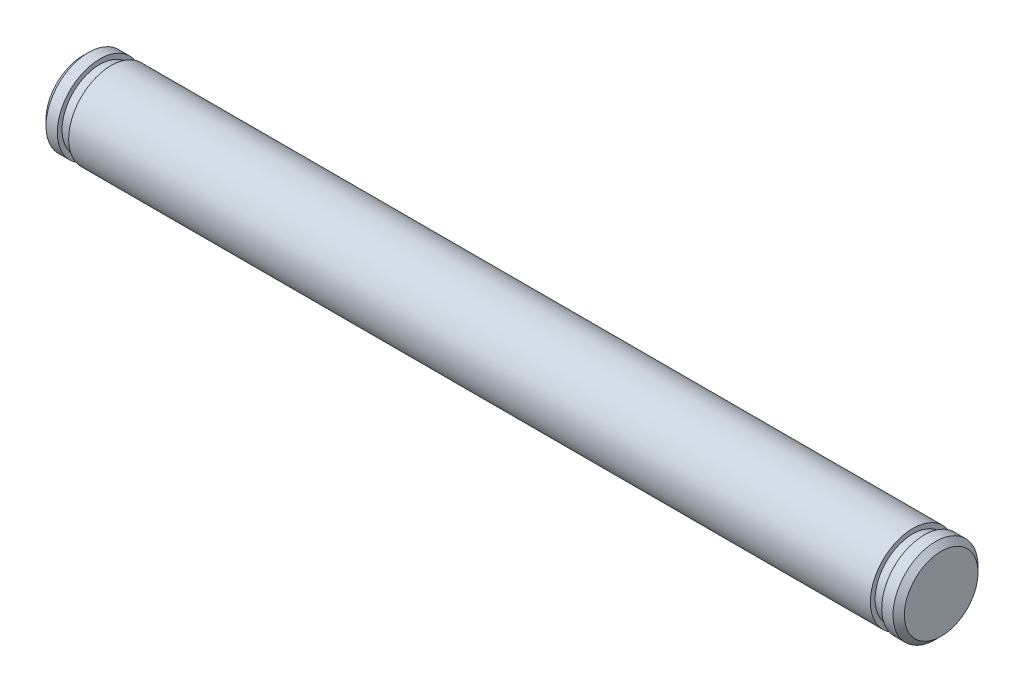
SolidWorks part; units mm, degrees
material "AISI 1020"
ref_plane "Front" through (0, 0, 0) normal (0, 0, 1) x (1, 0, 0)
ref_plane "Top" through (0, 0, 0) normal (0, 1, 0) x (1, 0, 0)
ref_plane "Right" through (0, 0, 0) normal (1, 0, 0) x (0, 0, -1)
ref_axis "side-side" through (80.9, 0, 0) along (-1, 0, 0)
ref_axis "up-down" through (0, 50, 0) along (0, -1, 0)
ref_axis "front-back" through (0, 0, -80.9) along (0, 0, 1)
sketch "Sketch1" plane through (0, 0, 0) normal (0, 0, 1) x (1, 0, 0)
  line L0 (-2, 0) -> (-12.9928, 0) construction
  line L1 (-2, 0) -> (58.602, 0)
  line L2 (-2, 0) -> (-2, 3)
  line L3 (-2, 3) -> (-0.8, 3)
  line L4 (58.602, 0) -> (58.602, 3)
  line L5 (0, 3) -> (56.602, 3)
  line L6 (57.402, 3) -> (58.602, 3)
  line L7 (-0.8, 3) -> (-0.8, 2.667)
  line L8 (-0.8, 2.667) -> (0, 2.667)
  line L9 (0, 3) -> (0, 2.667)
  line L11 (56.602, 3) -> (56.602, 2.667)
  line L12 (56.602, 2.667) -> (57.402, 2.667)
  line L13 (57.402, 3) -> (57.402, 2.667)
  point P10 (-0.4, 2.667)
  dimension "D1" = 6
  dimension "D2" = 5.334
  dimension "D3" = 0.8
  dimension "D4" = 1.2
  dimension "D5" = 56.602
revolve "Revolve1" add sketch "Sketch1" angle 360 about L0
chamfer "Chamfer1" distance 0.4 angle 45 2 edges at (-2, 3, 0) (58.602, 3, 0)
